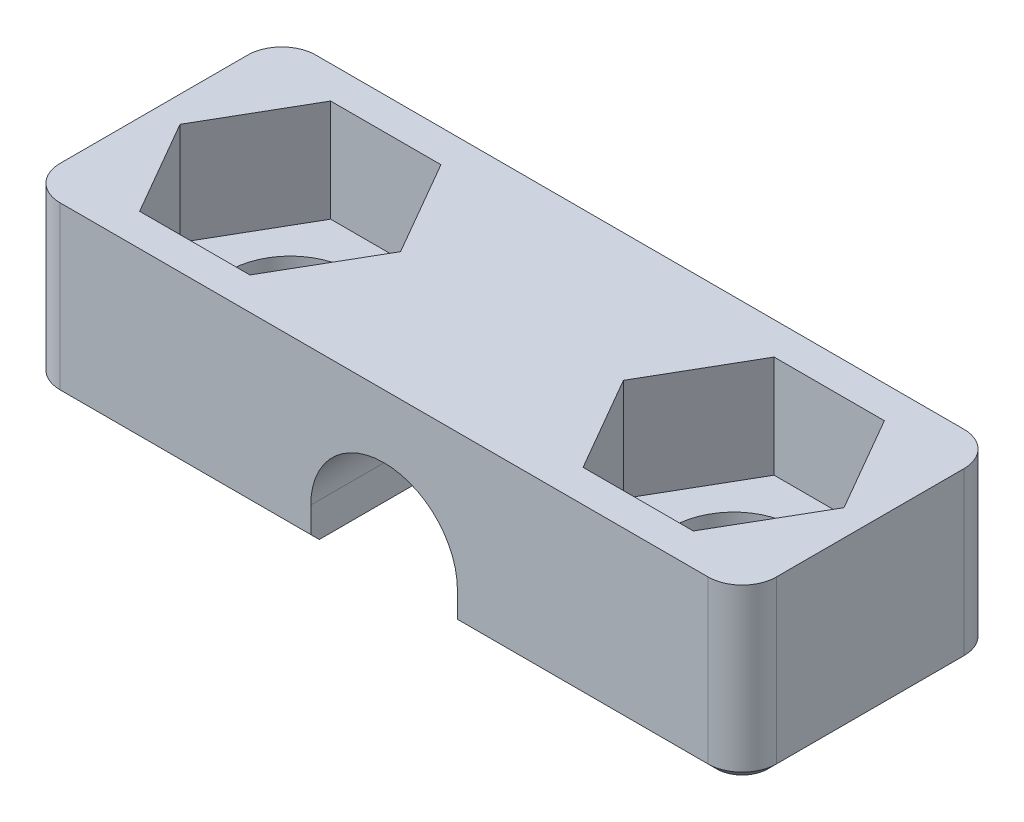
SolidWorks part; units mm, degrees
ref_plane "Front Plane" through (0, 0, 0) normal (0, 0, 1) x (1, 0, 0)
ref_plane "Top Plane" through (0, 0, 0) normal (0, 1, 0) x (1, 0, 0)
ref_plane "Right Plane" through (0, 0, 0) normal (1, 0, 0) x (0, 0, -1)
sketch "Sketch1" plane through (0, 0, 0) normal (0, 0, 1) x (1, 0, 0)
  line L0 (-2.15, 0) -> (-2.15, 1)
  line L1 (0, 0) -> (0, 7.323) construction
  line L2 (2.15, 0) -> (2.15, 1)
  line L3 (2.15, 0) -> (10.5, 0)
  line L4 (7.5, 0) -> (7.5, 3.1149) construction
  line L5 (10.5, 0) -> (10.5, 5)
  line L6 (10.5, 5) -> (-10.5, 5)
  line L7 (-2.15, 0) -> (-10.5, 0)
  line L8 (-10.5, 0) -> (-10.5, 5)
  arc A0 (-2.15, 1) -> (2.15, 1) centre (0, 1) cw
  point P16 (0, 5)
  dimension "D1" = 2.15
  dimension "D2" = 1
  dimension "D3" = 7.5
  dimension "D4" = 5
  dimension "D5" = 21
extrude "Extrude1" add sketch "Sketch1" along normal blind 7.5
sketch "Sketch2" plane through (0, 5, 0) normal (0, 1, 0) x (1, 0, 0)
  line L0 (0, 0) -> (0, -7.5) construction
  line L1 (10.5, -7.5) -> (-10.5, -7.5) construction
  line L2 (0, -3.75) -> (10.5, -3.75) construction
  line L3 (10.5, -7.5) -> (10.5, 0) construction
  line L4 (-8.1166, -6.55) -> (-9.7332, -3.75)
  line L5 (9.7332, -3.75) -> (8.1166, -0.95)
  line L6 (8.1166, -0.95) -> (4.8834, -0.95)
  line L7 (4.8834, -0.95) -> (3.2668, -3.75)
  line L8 (3.2668, -3.75) -> (4.8834, -6.55)
  line L9 (4.8834, -6.55) -> (8.1166, -6.55)
  line L10 (8.1166, -6.55) -> (9.7332, -3.75)
  line L11 (-4.8834, -6.55) -> (-8.1166, -6.55)
  line L12 (-3.2668, -3.75) -> (-4.8834, -6.55)
  line L13 (-4.8834, -0.95) -> (-3.2668, -3.75)
  line L14 (-8.1166, -0.95) -> (-4.8834, -0.95)
  line L15 (-9.7332, -3.75) -> (-8.1166, -0.95)
  circle A0 centre (6.5, -3.75) radius 1.8
  circle A1 centre (6.5, -3.75) radius 2.8 construction
  circle A2 centre (-6.5, -3.75) radius 1.8
  dimension "D2" = 3.6
  dimension "D1" = 13
  dimension "D3" = 5.6
extrude "Extrude2" cut sketch "Sketch2" against normal through all contours A2 | A0 region at (6.5, 5, 3.75) region at (-6.5, 5, 3.75)
extrude "Extrude3" cut sketch "Sketch" against normal blind 3
sketch "Sketch" plane through (0, 5, 0) normal (0, 1, 0) x (1, 0, 0) same geometry as "Sketch2"
fillet "Fillet1" radius 1 4 edges at (10.5, 2.5, 0) (10.5, 2.5, 7.5) (-10.5, 2.5, 0) (-10.5, 2.5, 7.5)
chamfer "Chamfer1" distance 0.25 angle 45 12 edges at (-8.3, 0, 3.75) (4.7, 0, 3.75) (5.825, 0, 0) (10.2071, 0, 0.2929) (10.5, 0, 3.75) (10.2071, 0, 7.2071) (5.825, 0, 7.5) (-5.825, 0, 0) (-10.2071, 0, 0.2929) (-10.5, 0, 3.75) (-10.2071, 0, 7.2071) (-5.825, 0, 7.5)
